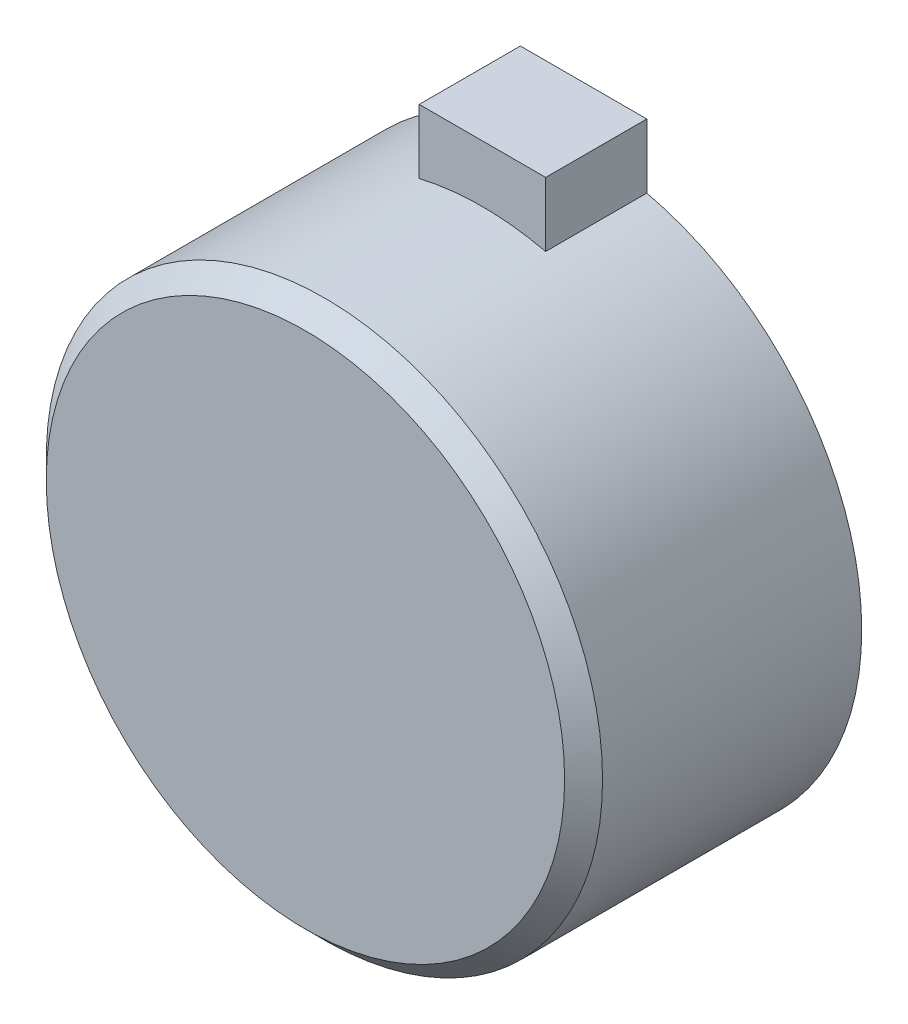
SolidWorks part; units mm, degrees
ref_plane "Front Plane" through (0, 0, 0) normal (0, 0, 1) x (1, 0, 0)
ref_plane "Top Plane" through (0, 0, 0) normal (0, 1, 0) x (1, 0, 0)
ref_plane "Right Plane" through (0, 0, 0) normal (1, 0, 0) x (0, 0, -1)
sketch "SK_Body" plane through (0, 0, 0) normal (0, 1, 0) x (1, 0, 0)
  line L0 (0, -10) -> (0, 54) construction
  line L1 (0, 0) -> (41, 0)
  line L2 (41, 0) -> (44, 3)
  line L3 (44, 3) -> (44, 44)
  line L4 (44, 44) -> (41, 44)
  line L5 (41, 44) -> (0, 44)
  line L6 (0, 44) -> (0, 0)
  dimension "P1" = 10
  dimension "P2" = 54
  dimension "R_front" = 41
  dimension "P4" = 44
  dimension "P5" = 3
  dimension "R_body" = 44
  dimension "L_body" = 44
  dimension "P8" = 41
  dimension "P9" = 44
  dimension "P10" = 44
revolve "Housing_Body" add sketch "SK_Body" angle 360 about L0
ref_plane "PL_Rear" through (0, 0, -44) normal (0, 0, 1) x (1, 0, 0)
sketch "SK_RearHole" plane through (0, 0, -44) normal (0, 0, 1) x (1, 0, 0)
  circle A0 centre (37, 0) radius 1.25
  dimension "D_rh" = 2.5
  dimension "R_rh" = 37
extrude "Rear_Tapped_Hole" cut sketch "SK_RearHole" along normal blind 8
ref_axis "AX_Joint" through (0, 0, -46.2) along (0, 0, 1)
pattern_circular "Rear_Hole_Pattern" count 6 over 360 about axis through (0, 0, -46.2) along (0, 0, 1) of "Rear_Tapped_Hole"
sketch "SK_Connector" plane through (0, 0, -44) normal (0, 0, 1) x (1, 0, 0)
  line L0 (-10, 40) -> (10, 40)
  line L1 (10, 40) -> (10, 53)
  line L2 (10, 53) -> (-10, 53)
  line L3 (-10, 53) -> (-10, 40)
  dimension "P1" = 10
  dimension "P2" = 40
  dimension "P3" = 10
  dimension "P4" = 40
  dimension "P5" = 10
  dimension "P6" = 53
  dimension "P7" = 10
  dimension "P8" = 53
extrude "Connector_Zone" add sketch "SK_Connector" along normal blind 16
equation "\"D_act\" = 88"
equation "\"L_housing\" = 44"
equation "\"PCD_rear\" = 74"
equation "\"D_rear_hole\" = 2.5"
equation "\"D_bearing_boss\" = 52"
equation "\"R_front@SK_Body\" = \"D_act\"/2-3.0"
equation "\"R_body@SK_Body\" = \"D_act\"/2"
equation "\"L_body@SK_Body\" = \"L_housing\""
equation "\"D_rh@SK_RearHole\" = \"D_rear_hole\""
equation "\"R_rh@SK_RearHole\" = \"PCD_rear\"/2"
